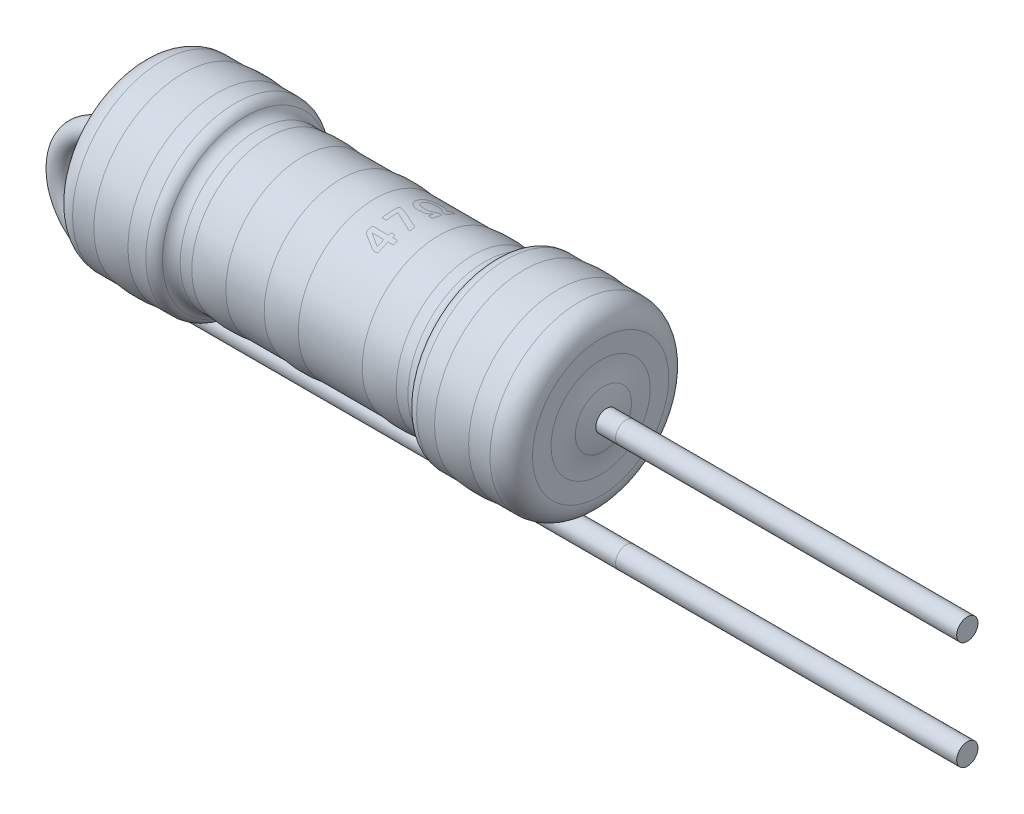
SolidWorks part; units mm, degrees
ref_plane "Front Plane" through (0, 0, 0) normal (0, 0, 1) x (1, 0, 0)
ref_plane "Top Plane" through (0, 0, 0) normal (0, 1, 0) x (1, 0, 0)
ref_plane "Right Plane" through (0, 0, 0) normal (1, 0, 0) x (0, 0, -1)
sketch "Sketch Set Wire Width" plane through (0, 0, 0) normal (0, 0, 1) x (1, 0, 0)
  line L0 (0, 0) -> (6, 0)
  line L1 (6, -2.54) -> (-6, -2.54)
  line L2 (6, 0) -> (14.0102, 0)
  line L3 (-6, 0) -> (-6, -2.54) construction
  line L4 (-6, 0) -> (-6, -2.54) construction
  line L5 (6, -2.54) -> (6, 0) construction
  line L6 (6, -2.54) -> (14.0102, -2.54)
  line L7 (14.0102, -2.54) -> (14.0102, 0) construction
  line L8 (-6, 0) -> (0, 0)
  arc A0 (-6, 0) -> (-6, -2.54) centre (-6, -1.27) ccw
  dimension "D2" = 2.54
  dimension "D3" = 30
  dimension "D1" = 12
  dimension "D4" = 6
sketch "Sketch Wire Diameter" plane through (0, 0, 0) normal (1, 0, 0) x (0, 0, -1)
  circle A0 centre (0, 0) radius 0.25
  dimension "D1" = 0.5
sweep "SET WIRE LENGTH" add profiles "Sketch Wire Diameter" path "Sketch Set Wire Width"
sketch "Sketch3" plane through (0, 0, 0) normal (0, 0, 1) x (1, 0, 0)
  line L0 (-5.4, 0) -> (5.4, 0)
  line L1 (0, 0) -> (0, 1.8) construction
  line L2 (-2.9, 1.8) -> (2.9, 1.8)
  line L3 (-5.4, 0) -> (-5.4, 1.6)
  line L4 (-4.9, 2.1) -> (-3.18, 2.1)
  line L5 (-2.9, 1.82) -> (-2.9, 1.8)
  line L6 (5.4, 0) -> (5.4, 1.6)
  line L7 (4.9, 2.1) -> (3.18, 2.1)
  line L8 (2.9, 1.82) -> (2.9, 1.8)
  arc A0 (-5.4, 1.6) -> (-4.9, 2.1) centre (-4.9, 1.6) cw
  arc A1 (5.4, 1.6) -> (4.9, 2.1) centre (4.9, 1.6) ccw
  arc A2 (-3.18, 2.1) -> (-2.9, 1.82) centre (-3.18, 1.82) cw
  arc A3 (3.18, 2.1) -> (2.9, 1.82) centre (3.18, 1.82) ccw
  dimension "D5" = 0.5
  dimension "D6" = 0.28
  dimension "D1" = 10.8
  dimension "D2" = 5.8
  dimension "D3" = 1.8
  dimension "D4" = 2.1
revolve "Revolve2" add sketch "Sketch3" angle 360 about L0
fillet "Fillet1" radius 0.3 2 edges at (2.9, 0, 1.8) (-2.9, 0, 1.8)
sketch "Sketch5" plane through (0, 0, 0) normal (0, 0, 1) x (1, 0, 0)
  line L0 (0, 0) -> (2, 0) construction
  line L1 (0, 0) -> (-0.3, 0) construction
  line L2 (-0.3, 0) -> (-2, 0) construction
  line L3 (-2, 0) -> (-4, 0) construction
  line L4 (2, 0) -> (4, 0) construction
  line L5 (-4, 0) -> (-4, 2.1) construction
  line L6 (-0.3, 0) -> (-0.3, 1.8) construction
  line L7 (-2, 0) -> (-2, 1.8) construction
  line L8 (2, 0) -> (2, 1.8) construction
  line L9 (4, 0) -> (4, 2.1) construction
  line L10 (-4, 2.1) -> (-4, 2.13) construction
  line L11 (-4.9, 2.1) -> (-3.18, 2.1) construction
  line L12 (4.9, 2.1) -> (3.18, 2.1) construction
  line L13 (-2.9, 1.8) -> (2.9, 1.8) construction
  line L14 (-2, 1.8) -> (-2, 1.83) construction
  line L17 (-4.4, 2.1) -> (-3.6, 2.1)
  line L19 (-5.4, 0) -> (5.4, 0) construction
  line L22 (-2.4, 1.8) -> (-1.6, 1.8) construction
  line L26 (-0.7, 1.8) -> (0.1, 1.8) construction
  line L30 (1.6, 1.8) -> (2.4, 1.8) construction
  line L34 (3.6, 2.1) -> (4.4, 2.1) construction
  line L36 (-0.3, 1.8) -> (-0.3, 1.83) construction
  line L37 (2, 1.8) -> (2, 1.83) construction
  line L38 (4, 2.1) -> (4, 2.13) construction
  arc A0 (-4.4, 2.1) -> (-3.6, 2.1) centre (-4, -0.5517) cw
  arc A1 (-2.4, 1.8) -> (-1.6, 1.8) centre (-2, -0.8517) cw construction
  arc A2 (-0.7, 1.8) -> (0.1, 1.8) centre (-0.3, -0.8517) cw construction
  arc A3 (1.6, 1.8) -> (2.4, 1.8) centre (2, -0.8517) cw construction
  arc A4 (3.6, 2.1) -> (4.4, 2.1) centre (4, -0.5517) cw construction
  dimension "D3" = 0.8
  dimension "D1" = 4
  dimension "D2" = 4
  dimension "D4" = 0.03
  dimension "D5" = 2
  dimension "D6" = 2
  dimension "D7" = 1.7
revolve "Band 1" add sketch "Sketch5" angle 360 about L2
sketch "Sketch8" plane through (0, 0, 0) normal (0, 0, 1) x (1, 0, 0)
  line L0 (-2.4, 1.8) -> (-1.6, 1.8) construction
  line L1 (-2.4, 1.8) -> (-1.6, 1.8)
  arc A0 (-1.6, 1.8) -> (-2.4, 1.8) centre (-2, -0.8517) ccw construction
  arc A1 (-1.6, 1.8) -> (-2.4, 1.8) centre (-2, -0.8517) ccw
revolve "Band 2" add sketch "Sketch8" angle 360 about L2
sketch "Sketch9" plane through (0, 0, 0) normal (0, 0, 1) x (1, 0, 0)
  line L0 (-0.7, 1.8) -> (0.1, 1.8) construction
  line L1 (-0.7, 1.8) -> (0.1, 1.8)
  arc A0 (0.1, 1.8) -> (-0.7, 1.8) centre (-0.3, -0.8517) ccw construction
  arc A1 (0.1, 1.8) -> (-0.7, 1.8) centre (-0.3, -0.8517) ccw
revolve "Band 3" add sketch "Sketch9" angle 360 about L2
sketch "Sketch10" plane through (0, 0, 0) normal (0, 0, 1) x (1, 0, 0)
  line L0 (1.6, 1.8) -> (2.4, 1.8) construction
  line L1 (1.6, 1.8) -> (2.4, 1.8)
  arc A0 (2.4, 1.8) -> (1.6, 1.8) centre (2, -0.8517) ccw construction
  arc A1 (2.4, 1.8) -> (1.6, 1.8) centre (2, -0.8517) ccw
revolve "Band 4" add sketch "Sketch10" angle 360 about L0
sketch "Sketch11" plane through (0, 0, 0) normal (0, 0, 1) x (1, 0, 0)
  line L0 (3.6, 2.1) -> (4.4, 2.1) construction
  line L1 (3.6, 2.1) -> (4.4, 2.1)
  arc A0 (4.4, 2.1) -> (3.6, 2.1) centre (4, -0.5517) ccw construction
  arc A1 (4.4, 2.1) -> (3.6, 2.1) centre (4, -0.5517) ccw
revolve "Band 5" add sketch "Sketch11" angle 360 about L4
sketch "Sketch12" plane through (0, 0, 0) normal (0, 0, 1) x (1, 0, 0)
  line L0 (-5.35, 0) -> (5.35, 0) construction
  line L1 (-5.35, 1) -> (-5.35, 0)
  line L2 (5.35, 1) -> (5.35, 0)
  line L3 (-5.35, 0) -> (-5.55, 0)
  line L4 (5.35, 0) -> (5.55, 0)
  arc A0 (-5.35, 1) -> (-5.55, 0) centre (-2.95, 0) ccw
  arc A1 (5.35, 1) -> (5.55, 0) centre (2.95, 0) cw
  dimension "D3" = 0.2
  dimension "D4" = 2.6
  dimension "D1" = 10.7
  dimension "D2" = 1
revolve "Revolve10" add sketch "Sketch12" angle 360 about L0
fillet "Fillet2" radius 2 2 edges at (5.4, 0, 0.8703) (-5.4, 0, -0.8703)
ref_plane "Plane2" through (0, 3, 0) normal (0, 1, 0) x (1, 0, 0)
sketch "Sketch13" plane through (0, 3, 0) normal (0, 1, 0) x (1, 0, 0)
  line L0 (0, 0) -> (1.15, 0) construction
  line L1 (1.15, 1.75) -> (1.15, -1.75) construction
  text T0 "47Ω" font "Calibri" height 0.6
  dimension "D1" = 3.5
  dimension "D2" = 1.15
wrap "Wrap1" sketch "Sketch13" wrap type scribe source sketch "Sketch13" face at (0.1, 1.8, 0)
